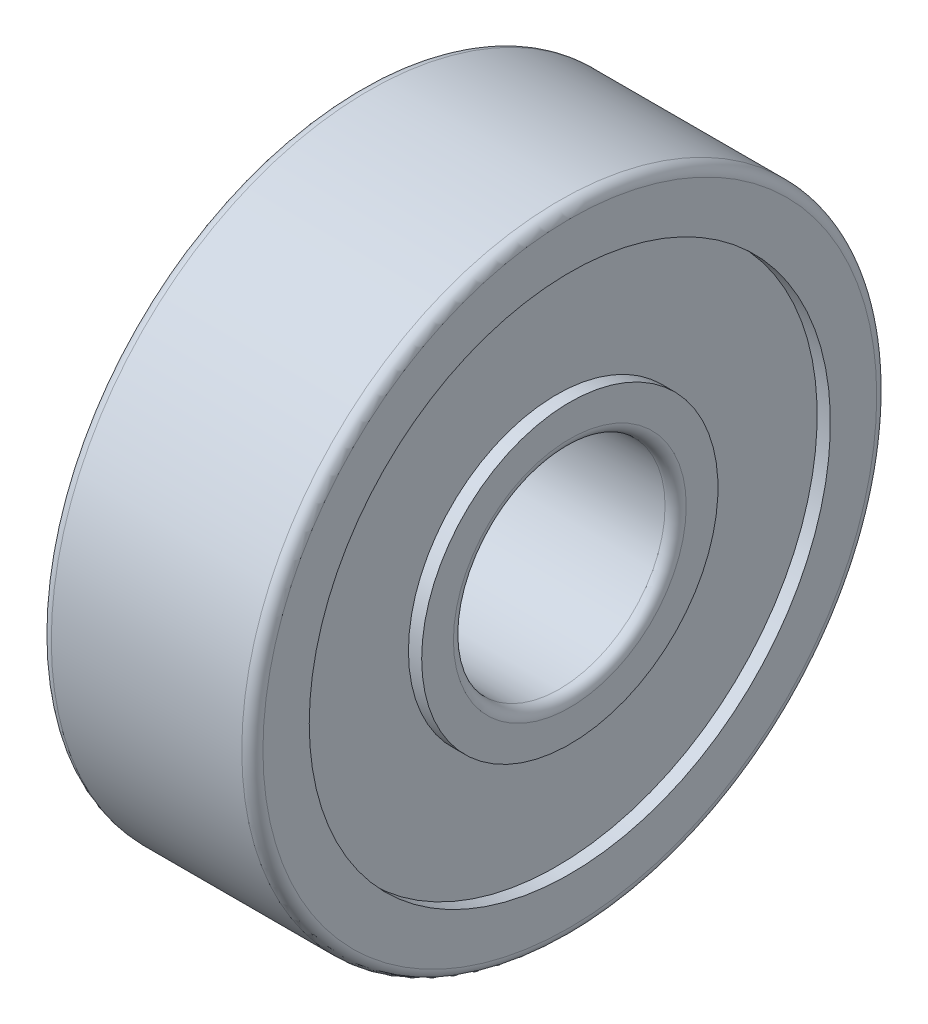
SolidWorks part; units mm, degrees
ref_plane "Front Plane" through (0, 0, 0) normal (0, 0, 1) x (1, 0, 0)
ref_plane "Top Plane" through (0, 0, 0) normal (0, 1, 0) x (1, 0, 0)
ref_plane "Right Plane" through (0, 0, 0) normal (1, 0, 0) x (0, 0, -1)
ref_axis "Axis_X" through (-0.2, 0, 0) along (1, 0, 0)
ref_axis "Axis_Y" through (0, 6.6, 0) along (0, -1, 0)
ref_axis "Axis_Z" through (0, 0, -6.6) along (0, 0, 1)
sketch "Sketch1" plane through (0, 0, 0) normal (0, 0, 1) x (1, 0, 0)
  line L0 (0, 0) -> (4, 0) construction
  line L1 (0, 4.925) -> (0.25, 4.925)
  line L2 (0.2, 6) -> (3.8, 6)
  line L3 (0, 5.8) -> (0, 4.925)
  line L4 (0.2, 2) -> (3.8, 2)
  line L5 (4, 5.8) -> (4, 4.925)
  line L6 (0, 6) -> (4, 2) construction
  line L7 (0, 2) -> (4, 6) construction
  line L8 (0.25, 4.925) -> (0.25, 2.8)
  line L9 (0.25, 2.8) -> (0, 2.8)
  line L10 (4, 4.925) -> (3.75, 4.925)
  line L11 (3.75, 4.925) -> (3.75, 2.8)
  line L12 (3.75, 2.8) -> (4, 2.8)
  line L13 (0, 2.8) -> (0, 2.2)
  line L14 (4, 2.8) -> (4, 2.2)
  arc A0 (0.2, 2) -> (0, 2.2) centre (0.2, 2.2) cw
  arc A1 (4, 2.2) -> (3.8, 2) centre (3.8, 2.2) cw
  arc A2 (4, 5.8) -> (3.8, 6) centre (3.8, 5.8) ccw
  arc A3 (0.2, 6) -> (0, 5.8) centre (0.2, 5.8) ccw
  point P3 (2, 4)
  dimension "R_s" = 0.2
  dimension "B" = 4
  dimension "D_s" = 4
  dimension "D" = 12
  dimension "MSM_1" = 5.6
  dimension "MSM_2" = 9.85
  dimension "MSM_3" = 0.25
revolve "Revolve1" add sketch "Sketch1" angle 360 about axis through (-0.2, 0, 0) along (1, 0, 0)
equation "\"Factor\"= 1.082532"
